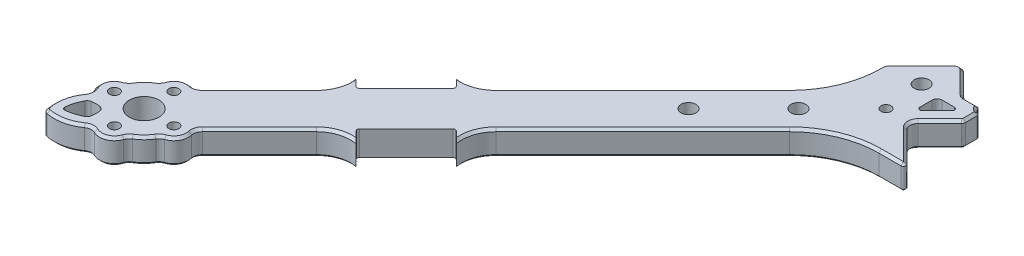
SolidWorks part; units mm, degrees
ref_plane "前视基准面" through (0, 0, 0) normal (0, 0, 1) x (1, 0, 0)
ref_plane "上视基准面" through (0, 0, 0) normal (0, 1, 0) x (1, 0, 0)
ref_plane "右视基准面" through (0, 0, 0) normal (1, 0, 0) x (0, 0, -1)
sketch "草图1" plane through (0, 0, 0) normal (0, 1, 0) x (1, 0, 0)
  line L0 (0, 0) -> (0, 44.7122) construction
  line L1 (-46.659, 0) -> (34.6836, 0) construction
  line L2 (3.067, 3.067) -> (44.142, 44.142) construction
  line L3 (0, 0) -> (-41.075, 41.075) construction
  line L4 (64.7943, 159.7121) -> (139.6536, 139.6536) construction
  line L5 (-139.6536, 139.6536) -> (-159.7121, 64.7943) construction
  line L6 (-159.7121, 64.7943) -> (-104.9113, 9.9936) construction
  line L7 (-104.9113, 9.9936) -> (-30.052, 30.052) construction
  line L8 (-30.052, 30.052) -> (-9.9936, 104.9113) construction
  line L9 (-9.9936, 104.9113) -> (-64.7943, 159.7121) construction
  line L10 (-64.7943, 159.7121) -> (-139.6536, 139.6536) construction
  line L11 (9.9936, 104.9113) -> (64.7943, 159.7121) construction
  line L12 (30.052, 30.052) -> (9.9936, 104.9113) construction
  line L13 (104.9113, 9.9936) -> (30.052, 30.052) construction
  line L14 (159.7121, 64.7943) -> (104.9113, 9.9936) construction
  line L15 (139.6536, 139.6536) -> (159.7121, 64.7943) construction
  line L16 (-64.7943, -159.7121) -> (-139.6536, -139.6536) construction
  line L17 (-9.9936, -104.9113) -> (-64.7943, -159.7121) construction
  line L18 (-30.052, -30.052) -> (-9.9936, -104.9113) construction
  line L19 (-104.9113, -9.9936) -> (-30.052, -30.052) construction
  line L20 (-159.7121, -64.7943) -> (-104.9113, -9.9936) construction
  line L21 (-139.6536, -139.6536) -> (-159.7121, -64.7943) construction
  line L22 (9.9936, -104.9113) -> (64.7943, -159.7121) construction
  line L23 (30.052, -30.052) -> (9.9936, -104.9113) construction
  line L24 (104.9113, -9.9936) -> (30.052, -30.052) construction
  line L25 (159.7121, -64.7943) -> (104.9113, -9.9936) construction
  line L26 (139.6536, -139.6536) -> (159.7121, -64.7943) construction
  line L27 (64.7943, -159.7121) -> (139.6536, -139.6536) construction
  line L28 (-90.8528, -84.8528) -> (-84.8528, -90.8528) construction
  line L29 (-10, 10) -> (10, 10) construction
  line L30 (-10, 10) -> (-10, -10) construction
  line L31 (-10, -10) -> (10, -10) construction
  line L32 (10, 10) -> (10, -10) construction
  line L33 (-10, 10) -> (10, -10) construction
  line L34 (-10, -10) -> (10, 10) construction
  line L35 (-90.8528, -84.8528) -> (-84.8528, -78.8528) construction
  line L36 (-84.8528, -90.8528) -> (-78.8528, -84.8528) construction
  line L37 (-84.8528, -78.8528) -> (-78.8528, -84.8528) construction
  line L38 (-90.8528, -84.8528) -> (-78.8528, -84.8528) construction
  line L39 (-84.8528, -90.8528) -> (-84.8528, -78.8528) construction
  line L40 (-83.3357, -76.2647) -> (-76.2647, -69.1936) construction
  line L41 (-76.2647, -83.3357) -> (-69.1936, -76.2647) construction
  line L42 (-40, -21.5) -> (-21.5, -40) construction
  line L43 (-25.5, 43.5) -> (25.5, 43.5) construction
  line L44 (-25.5, 43.5) -> (-25.5, -43.5) construction
  line L45 (-25.5, -43.5) -> (25.5, -43.5) construction
  line L46 (25.5, 43.5) -> (25.5, -43.5) construction
  line L47 (-25.5, 43.5) -> (25.5, -43.5) construction
  line L48 (-25.5, -43.5) -> (25.5, 43.5) construction
  line L49 (-21.5, -40) -> (-21.5, -21.5) construction
  line L50 (-1.05, -0.05) -> (-3.8789, -0.05)
  line L51 (-4.586, 0.2429) -> (-8.9393, 4.5962)
  line L52 (-0.05, -1.05) -> (-0.05, -3.8789) construction
  line L53 (-11.0607, 4.5962) -> (-17.4142, -1.7574)
  line L54 (-18, -3.1716) -> (-18, -3.4731)
  line L55 (-23.2721, -16.201) -> (-82.5161, -75.445)
  line L56 (-0.05, 1.05) -> (-0.05, 3.8789) construction
  line L57 (0.2429, 4.586) -> (4.5962, 8.9393) construction
  line L58 (4.5962, 11.0607) -> (-1.7574, 17.4142) construction
  line L59 (-3.1716, 18) -> (-3.4731, 18) construction
  line L60 (1.05, 0.05) -> (3.8789, 0.05) construction
  line L61 (4.586, -0.2429) -> (8.9393, -4.5962) construction
  line L62 (11.0607, -4.5962) -> (17.4142, 1.7574) construction
  line L63 (18, 3.1716) -> (18, 3.4731) construction
  line L64 (0.05, -1.05) -> (0.05, -3.8789) construction
  line L65 (-0.2429, -4.586) -> (-4.5962, -8.9393) construction
  line L66 (-4.5962, -11.0607) -> (1.7574, -17.4142) construction
  line L67 (3.1716, -18) -> (3.4731, -18) construction
  line L68 (-0.05, -1.05) -> (-0.05, -3.8789)
  line L69 (-0.3136, -4.5153) -> (-4.6669, -8.8686)
  line L70 (-75.445, -82.5161) -> (-16.201, -23.2721)
  line L71 (-3.4731, -18) -> (0.9946, -18)
  line L72 (3.1716, -18.1) -> (3.4731, -18.1) construction
  line L73 (-4.6669, -11.1314) -> (1.6866, -17.4849) construction
  line L74 (-4.6669, -11.1314) -> (1.3482, -17.1464)
  line L75 (-3.35, -2.85) -> (-5.85, -2.85)
  line L76 (-6.85, -3.85) -> (-6.85, -6.35)
  line L77 (-5.9964, -6.7036) -> (-2.9964, -3.7036)
  line L78 (-21.5, -40) -> (-38.3673, -19.8673) construction
  circle A0 centre (-84.8528, 84.8528) radius 77.5 construction
  circle A1 centre (-84.8528, 84.8528) radius 83 construction
  circle A2 centre (84.8528, 84.8528) radius 77.5 construction
  circle A3 centre (84.8528, 84.8528) radius 83 construction
  circle A4 centre (84.8528, -84.8528) radius 77.5 construction
  circle A5 centre (84.8528, -84.8528) radius 83 construction
  circle A6 centre (-84.8528, -84.8528) radius 83 construction
  circle A7 centre (-84.8528, -84.8528) radius 77.5 construction
  circle A8 centre (-84.8528, 84.8528) radius 67.117 construction
  circle A9 centre (10, 10) radius 1 construction
  circle A10 centre (-10, 10) radius 1 construction
  circle A11 centre (-10, -10) radius 1
  circle A12 centre (10, -10) radius 1 construction
  circle A13 centre (-84.8528, -84.8528) radius 6 construction
  circle A14 centre (-84.8528, -78.8528) radius 1
  circle A15 centre (-90.8528, -84.8528) radius 1
  circle A16 centre (-84.8528, -90.8528) radius 1
  circle A17 centre (-78.8528, -84.8528) radius 1
  circle A18 centre (-84.8528, -84.8528) radius 3
  circle A19 centre (-84.8528, -84.8528) radius 7 construction
  circle A20 centre (-84.8528, -78.8528) radius 3 construction
  circle A21 centre (-90.8528, -84.8528) radius 3 construction
  circle A22 centre (-84.8528, -90.8528) radius 3 construction
  circle A23 centre (-78.8528, -84.8528) radius 3 construction
  arc A24 (-84.1878, -75.9274) -> (-82.5161, -75.445) centre (-83.7889, -74.1722) ccw
  arc A25 (-84.1878, -75.9274) -> (-87.6956, -77.8945) centre (-84.8528, -78.8528) ccw
  arc A26 (-88.4709, -78.8604) -> (-90.8452, -81.2347) centre (-84.8528, -84.8528) ccw
  arc A27 (-91.8111, -82.01) -> (-93.5405, -86.1856) centre (-90.8528, -84.8528) ccw
  arc A28 (-90.8452, -81.2347) -> (-91.8111, -82.01) centre (-92.3861, -80.3043) cw
  arc A29 (-87.6956, -77.8945) -> (-88.4709, -78.8604) centre (-89.4013, -77.3195) cw
  arc A30 (-95.0261, -94.2399) -> (-93.6885, -88.0317) centre (-87.1792, -92.6823) cw
  arc A31 (-93.5405, -86.1856) -> (-93.6885, -88.0317) centre (-95.1531, -86.9853) cw
  arc A32 (-94.2399, -95.0261) -> (-88.0317, -93.6885) centre (-92.6823, -87.1792) ccw
  arc A33 (-86.1856, -93.5405) -> (-88.0317, -93.6885) centre (-86.9853, -95.1531) ccw
  arc A34 (-82.01, -91.8111) -> (-86.1856, -93.5405) centre (-84.8528, -90.8528) cw
  arc A35 (-81.2347, -90.8452) -> (-82.01, -91.8111) centre (-80.3043, -92.3861) ccw
  arc A36 (-78.8604, -88.4709) -> (-81.2347, -90.8452) centre (-84.8528, -84.8528) cw
  arc A37 (-77.8945, -87.6956) -> (-78.8604, -88.4709) centre (-77.3195, -89.4013) ccw
  arc A38 (-75.9274, -84.1878) -> (-77.8945, -87.6956) centre (-78.8528, -84.8528) cw
  arc A39 (-75.9274, -84.1878) -> (-75.445, -82.5161) centre (-74.1722, -83.7889) cw
  arc A40 (-95.0261, -94.2399) -> (-94.2399, -95.0261) centre (-94.0452, -94.0452) ccw
  arc A41 (-89.7377, -88.9059) -> (-91.477, -88.9335) centre (-90.5281, -93.9108) ccw
  arc A42 (-92.1608, -89.4245) -> (-93.1294, -92.591) centre (-85.4545, -93.2074) ccw
  arc A43 (-89.4245, -92.1608) -> (-92.591, -93.1294) centre (-93.2074, -85.4545) cw
  arc A44 (-88.9059, -89.7377) -> (-88.9335, -91.477) centre (-93.9108, -90.5281) cw
  arc A45 (-89.4245, -92.1608) -> (-88.9335, -91.477) centre (-89.9158, -91.2898) ccw
  arc A46 (-89.7377, -88.9059) -> (-88.9059, -89.7377) centre (-89.8937, -89.8937) cw
  arc A47 (-91.477, -88.9335) -> (-92.1608, -89.4245) centre (-91.2898, -89.9158) ccw
  arc A48 (-93.1294, -92.591) -> (-92.591, -93.1294) centre (-92.631, -92.631) ccw
  circle A49 centre (-21.5, -40) radius 3.1 construction
  circle A50 centre (-21.5, -40) radius 1.5 construction
  circle A51 centre (-40, -21.5) radius 1.5 construction
  circle A53 centre (-21.5, -21.5) radius 1.5 construction
  arc A54 (-3.8789, -0.05) -> (-4.586, 0.2429) centre (-3.8789, 0.95) cw
  arc A55 (-23.2721, -16.201) -> (-18, -3.4731) centre (-36, -3.4731) ccw
  arc A56 (-17.4142, -1.7574) -> (-18, -3.1716) centre (-16, -3.1716) ccw
  arc A57 (-8.9393, 4.5962) -> (-11.0607, 4.5962) centre (-10, 3.5355) ccw
  arc A58 (-1.05, -0.05) -> (-0.05, -1.05) centre (-1.05, -1.05) cw
  circle A59 centre (-10, 0) radius 1.5 construction
  arc A60 (-0.05, 3.8789) -> (0.2429, 4.586) centre (0.95, 3.8789) cw construction
  arc A61 (4.5962, 8.9393) -> (4.5962, 11.0607) centre (3.5355, 10) ccw construction
  arc A62 (-1.7574, 17.4142) -> (-3.1716, 18) centre (-3.1716, 16) ccw construction
  arc A63 (-16.201, 23.2721) -> (-3.4731, 18) centre (-3.4731, 36) ccw construction
  arc A64 (-0.05, 1.05) -> (-1.05, 0.05) centre (-1.05, 1.05) cw construction
  arc A65 (3.8789, 0.05) -> (4.586, -0.2429) centre (3.8789, -0.95) cw construction
  arc A66 (8.9393, -4.5962) -> (11.0607, -4.5962) centre (10, -3.5355) ccw construction
  arc A67 (17.4142, 1.7574) -> (18, 3.1716) centre (16, 3.1716) ccw construction
  arc A68 (23.2721, 16.201) -> (18, 3.4731) centre (36, 3.4731) ccw construction
  arc A69 (1.05, 0.05) -> (0.05, 1.05) centre (1.05, 1.05) cw construction
  arc A70 (0.05, -3.8789) -> (-0.2429, -4.586) centre (-0.95, -3.8789) cw construction
  arc A71 (-4.5962, -8.9393) -> (-4.5962, -11.0607) centre (-3.5355, -10) ccw construction
  arc A72 (1.7574, -17.4142) -> (3.1716, -18) centre (3.1716, -16) ccw construction
  arc A73 (16.201, -23.2721) -> (3.4731, -18) centre (3.4731, -36) ccw construction
  arc A74 (0.05, -1.05) -> (1.05, -0.05) centre (1.05, -1.05) cw construction
  arc A75 (-6.85, -6.35) -> (-5.9964, -6.7036) centre (-6.35, -6.35) ccw
  arc A76 (-0.05, -3.8789) -> (-0.3136, -4.5153) centre (-0.95, -3.8789) cw
  arc A77 (-4.6669, -8.8686) -> (-4.6669, -11.1314) centre (-3.5355, -10) ccw
  arc A78 (-16.201, -23.2721) -> (-3.4731, -18) centre (-3.4731, -36) cw
  arc A79 (0.9946, -18) -> (1.3482, -17.1464) centre (0.9946, -17.5) ccw
  arc A80 (16.1303, -23.3428) -> (3.4731, -18.1) centre (3.4731, -36) ccw construction
  arc A81 (1.6866, -17.4849) -> (3.1716, -18.1) centre (3.1716, -16) ccw construction
  arc A82 (-0.05, -1.05) -> (1.05, 0.05) centre (1.05, -1.05) cw construction
  arc A83 (-3.35, -2.85) -> (-2.9964, -3.7036) centre (-3.35, -3.35) cw
  arc A84 (-5.85, -2.85) -> (-6.85, -3.85) centre (-5.85, -3.85) ccw
  circle A87 centre (-38.3673, -19.8673) radius 1.5
  circle A88 centre (-38.3673, -19.8673) radius 2.4 construction
  circle A89 centre (-29.9337, -29.9337) radius 1.5
  circle A90 centre (-18.8388, -18.8388) radius 1.5
  circle A91 centre (-10.7071, -2.1213) radius 1.5
  circle A92 centre (-3.6338, -15.7) radius 1 construction
  point P47 (0, 0)
  point P85 (-91.1861, -81.8714)
  point P88 (-87.8342, -78.5195)
  point P95 (-94.8733, -94.8733)
  point P96 (-94.7523, -94.7523)
  point P115 (0, 0)
  point P122 (-89.0416, -91.9299)
  point P125 (-89.061, -89.061)
  point P128 (-91.9299, -89.0416)
  point P131 (-93.1539, -93.1539)
  point P158 (-10, 5.6569)
  point P163 (-0.05, -0.05)
  point P212 (0, 0)
  point P231 (-16.201, -23.2721)
  point P242 (-29.9337, -29.9337)
  dimension "D2" = 155
  dimension "D4" = 166
  dimension "D5" = 2
  dimension "D6" = 12
  dimension "D7" = 2
  dimension "D8" = 6
  dimension "D9" = 6
  dimension "D11" = 1.8
  dimension "D13" = 8
  dimension "D15" = 1
  dimension "D16" = 1
  dimension "D17" = 0.5
  dimension "D22" = 6.2
  dimension "D23" = 3
  dimension "D26" = 1
  dimension "D27" = 1
  dimension "D30" = 1.5
  dimension "D31" = 18
  dimension "D32" = 2
  dimension "D35" = 0.5
  dimension "D37" = 0.5
  dimension "D38" = 1
  dimension "D41" = 21.5
  dimension "D42" = 40
  dimension "D43" = 4.8
  dimension "D47" = 2
  dimension "D1" = 20
  dimension "D3" = 120
  dimension "D10" = 10
  dimension "D12" = 14
  dimension "D14" = 4
  dimension "D18" = 2
  dimension "D19" = 10
  dimension "D20" = 51
  dimension "D21" = 87
  dimension "D24" = 0.05
  dimension "D25" = 45
  dimension "D28" = 4
  dimension "D29" = 8
  dimension "D36" = 0.05
  dimension "D39" = 2.8
  dimension "D40" = 2.5
  dimension "D44" = 12.5
  dimension "D45" = 5
  dimension "D46" = 6
  dimension "D48" = 2.3
  dimension "D49" = 2.5
  dimension "D34" = 0.1
  dimension "D33" = 4
extrude "凸台-拉伸1" add sketch "草图1" along normal blind 5 contours L71 A79 L74 A77 L69 A76 L68 A58 L50 A54 L51 A57 L53 A56 L54 A55 L55 A24 A25 A29 A26 A28 A27 A31 A30 A40 A32 A33 A34 A35 A36 A37 A38 A39 L70 A78 A84 L75 A83 L77 A75 L76 A11 A14 A15 A16
sketch "草图2" plane through (0, 5, 0) normal (0, 1, 0) x (1, 0, 0)
  line L0 (-2.85, 3.35) -> (-2.85, 5.85)
  line L1 (-6.7036, 5.9964) -> (-3.7036, 2.9964)
  line L2 (-3.85, 6.85) -> (-6.35, 6.85)
  line L3 (-3.35, -2.85) -> (-5.85, -2.85)
  line L4 (-5.9964, -6.7036) -> (-2.9964, -3.7036)
  line L5 (-6.85, -3.85) -> (-6.85, -6.35)
  line L6 (-3.35, -2.85) -> (-5.85, -2.85)
  line L7 (-5.9964, -6.7036) -> (-2.9964, -3.7036)
  line L8 (-6.85, -3.85) -> (-6.85, -6.35)
  line L9 (-18, 3.4731) -> (-18, -0.9946)
  line L10 (-17.1464, -1.3482) -> (-11.1314, 4.6669)
  line L11 (-8.8686, 4.6669) -> (-4.5153, 0.3136)
  line L12 (-3.8789, 0.05) -> (-1.05, 0.05)
  line L13 (-0.05, 1.05) -> (-0.05, 3.8789)
  line L14 (0.2429, 4.586) -> (4.5962, 8.9393)
  line L15 (4.5962, 11.0607) -> (-1.7574, 17.4142)
  line L16 (-3.4731, -18) -> (0.9946, -18)
  line L17 (1.3482, -17.1464) -> (-4.6669, -11.1314)
  line L18 (-4.6669, -8.8686) -> (-0.3136, -4.5153)
  line L19 (-0.05, -3.8789) -> (-0.05, -1.05)
  line L20 (-1.05, -0.05) -> (-3.8789, -0.05)
  line L21 (-4.586, 0.2429) -> (-8.9393, 4.5962)
  line L22 (-11.0607, 4.5962) -> (-17.4142, -1.7574)
  line L23 (-18, -3.1716) -> (-18, -3.4731)
  line L24 (-23.2721, -16.201) -> (-82.5161, -75.445)
  line L25 (-75.445, -82.5161) -> (-16.201, -23.2721)
  line L26 (-3.4731, -18) -> (0.9946, -18)
  line L27 (1.3482, -17.1464) -> (-4.6669, -11.1314)
  line L28 (-4.6669, -8.8686) -> (-0.3136, -4.5153)
  line L29 (-0.05, -3.8789) -> (-0.05, -1.05)
  line L30 (-1.05, -0.05) -> (-3.8789, -0.05)
  line L31 (-4.586, 0.2429) -> (-8.9393, 4.5962)
  line L32 (-11.0607, 4.5962) -> (-17.4142, -1.7574)
  line L33 (-18, -3.1716) -> (-18, -3.4731)
  line L34 (-23.2721, -16.201) -> (-82.5161, -75.445)
  line L35 (-75.445, -82.5161) -> (-16.201, -23.2721)
  line L36 (-3.1716, 18) -> (-3.4731, 18)
  line L37 (-16.201, 23.2721) -> (-75.445, 82.5161)
  line L38 (-82.5161, 75.445) -> (-23.2721, 16.201)
  line L39 (3.35, 2.85) -> (5.85, 2.85)
  line L40 (5.9964, 6.7036) -> (2.9964, 3.7036)
  line L41 (6.85, 3.85) -> (6.85, 6.35)
  line L42 (3.4731, 18) -> (-0.9946, 18)
  line L43 (-1.3482, 17.1464) -> (4.6669, 11.1314)
  line L44 (4.6669, 8.8686) -> (0.3136, 4.5153)
  line L45 (0.05, 3.8789) -> (0.05, 1.05)
  line L46 (1.05, 0.05) -> (3.8789, 0.05)
  line L47 (4.586, -0.2429) -> (8.9393, -4.5962)
  line L48 (11.0607, -4.5962) -> (17.4142, 1.7574)
  line L49 (18, 3.1716) -> (18, 3.4731)
  line L50 (23.2721, 16.201) -> (82.5161, 75.445)
  line L51 (75.445, 82.5161) -> (16.201, 23.2721)
  line L52 (2.85, -3.35) -> (2.85, -5.85)
  line L53 (6.7036, -5.9964) -> (3.7036, -2.9964)
  line L54 (3.85, -6.85) -> (6.35, -6.85)
  line L55 (18, -3.4731) -> (18, 0.9946)
  line L56 (17.1464, 1.3482) -> (11.1314, -4.6669)
  line L57 (8.8686, -4.6669) -> (4.5153, -0.3136)
  line L58 (3.8789, -0.05) -> (1.05, -0.05)
  line L59 (0.05, -1.05) -> (0.05, -3.8789)
  line L60 (-0.2429, -4.586) -> (-4.5962, -8.9393)
  line L61 (-4.5962, -11.0607) -> (1.7574, -17.4142)
  line L62 (3.1716, -18) -> (3.4731, -18)
  line L63 (16.201, -23.2721) -> (75.445, -82.5161)
  line L64 (82.5161, -75.445) -> (23.2721, -16.201)
  line L65 (-25.5, 43.5) -> (25.5, -43.5) construction
  line L66 (25.5, 43.5) -> (-25.5, 43.5) construction
  line L67 (25.5, 43.5) -> (25.5, -43.5) construction
  line L68 (25.5, -43.5) -> (-25.5, -43.5) construction
  line L69 (-25.5, 43.5) -> (-25.5, -43.5) construction
  line L70 (25.5, 43.5) -> (-25.5, -43.5) construction
  line L71 (25.5, -43.5) -> (-25.5, 43.5) construction
  circle A0 centre (-10, 10) radius 1
  circle A1 centre (-10, -10) radius 1
  circle A2 centre (-10, -10) radius 1
  arc A3 (-5.85, -2.85) -> (-6.85, -3.85) centre (-5.85, -3.85) ccw
  arc A4 (-2.9964, -3.7036) -> (-3.35, -2.85) centre (-3.35, -3.35) ccw
  arc A5 (-6.85, -6.35) -> (-5.9964, -6.7036) centre (-6.35, -6.35) ccw
  arc A6 (-5.85, -2.85) -> (-6.85, -3.85) centre (-5.85, -3.85) ccw
  arc A7 (-2.9964, -3.7036) -> (-3.35, -2.85) centre (-3.35, -3.35) ccw
  arc A8 (-6.85, -6.35) -> (-5.9964, -6.7036) centre (-6.35, -6.35) ccw
  circle A9 centre (-84.8528, -78.8528) radius 1
  circle A10 centre (-84.8528, -78.8528) radius 1
  circle A11 centre (-90.8528, -84.8528) radius 1
  circle A12 centre (-90.8528, -84.8528) radius 1
  circle A13 centre (-84.8528, -90.8528) radius 1
  circle A14 centre (-84.8528, -90.8528) radius 1
  circle A15 centre (-78.8528, -84.8528) radius 1
  circle A16 centre (-78.8528, -84.8528) radius 1
  circle A17 centre (-84.8528, -84.8528) radius 3
  circle A18 centre (-84.8528, -84.8528) radius 3
  circle A19 centre (-29.9337, -29.9337) radius 1.5 construction
  circle A21 centre (-18.8388, -18.8388) radius 1.5 construction
  arc A25 (-2.85, 5.85) -> (-3.85, 6.85) centre (-3.85, 5.85) ccw
  arc A26 (-93.1294, -92.591) -> (-92.591, -93.1294) centre (-92.631, -92.631) ccw
  arc A27 (-92.1608, -89.4245) -> (-93.1294, -92.591) centre (-85.4545, -93.2074) ccw
  arc A28 (-91.477, -88.9335) -> (-92.1608, -89.4245) centre (-91.2898, -89.9158) ccw
  arc A29 (-89.7377, -88.9059) -> (-91.477, -88.9335) centre (-90.5281, -93.9108) ccw
  arc A30 (-88.9059, -89.7377) -> (-89.7377, -88.9059) centre (-89.8937, -89.8937) ccw
  arc A31 (-88.9335, -91.477) -> (-88.9059, -89.7377) centre (-93.9108, -90.5281) ccw
  arc A32 (-89.4245, -92.1608) -> (-88.9335, -91.477) centre (-89.9158, -91.2898) ccw
  arc A33 (-92.591, -93.1294) -> (-89.4245, -92.1608) centre (-93.2074, -85.4545) ccw
  arc A34 (-93.1294, -92.591) -> (-92.591, -93.1294) centre (-92.631, -92.631) ccw
  arc A35 (-92.1608, -89.4245) -> (-93.1294, -92.591) centre (-85.4545, -93.2074) ccw
  arc A36 (-91.477, -88.9335) -> (-92.1608, -89.4245) centre (-91.2898, -89.9158) ccw
  arc A37 (-89.7377, -88.9059) -> (-91.477, -88.9335) centre (-90.5281, -93.9108) ccw
  arc A38 (-88.9059, -89.7377) -> (-89.7377, -88.9059) centre (-89.8937, -89.8937) ccw
  arc A39 (-88.9335, -91.477) -> (-88.9059, -89.7377) centre (-93.9108, -90.5281) ccw
  arc A40 (-89.4245, -92.1608) -> (-88.9335, -91.477) centre (-89.9158, -91.2898) ccw
  arc A41 (-92.591, -93.1294) -> (-89.4245, -92.1608) centre (-93.2074, -85.4545) ccw
  arc A42 (-3.7036, 2.9964) -> (-2.85, 3.35) centre (-3.35, 3.35) ccw
  arc A43 (-6.35, 6.85) -> (-6.7036, 5.9964) centre (-6.35, 6.35) ccw
  circle A44 centre (-78.8528, 84.8528) radius 1
  circle A45 centre (-84.8528, 90.8528) radius 1
  circle A46 centre (-90.8528, 84.8528) radius 1
  circle A47 centre (-84.8528, 78.8528) radius 1
  circle A48 centre (-84.8528, 84.8528) radius 3
  arc A52 (-92.591, 93.1294) -> (-93.1294, 92.591) centre (-92.631, 92.631) ccw
  arc A53 (-89.4245, 92.1608) -> (-92.591, 93.1294) centre (-93.2074, 85.4545) ccw
  arc A54 (-88.9335, 91.477) -> (-89.4245, 92.1608) centre (-89.9158, 91.2898) ccw
  arc A55 (-88.9059, 89.7377) -> (-88.9335, 91.477) centre (-93.9108, 90.5281) ccw
  arc A56 (-89.7377, 88.9059) -> (-88.9059, 89.7377) centre (-89.8937, 89.8937) ccw
  arc A57 (-91.477, 88.9335) -> (-89.7377, 88.9059) centre (-90.5281, 93.9108) ccw
  arc A58 (-92.1608, 89.4245) -> (-91.477, 88.9335) centre (-91.2898, 89.9158) ccw
  arc A59 (-93.1294, 92.591) -> (-92.1608, 89.4245) centre (-85.4545, 93.2074) ccw
  arc A60 (-18, -0.9946) -> (-17.1464, -1.3482) centre (-17.5, -0.9946) ccw
  arc A61 (-8.8686, 4.6669) -> (-11.1314, 4.6669) centre (-10, 3.5355) ccw
  arc A62 (-4.5153, 0.3136) -> (-3.8789, 0.05) centre (-3.8789, 0.95) ccw
  arc A63 (-1.05, 0.05) -> (-0.05, 1.05) centre (-1.05, 1.05) ccw
  arc A64 (0.2429, 4.586) -> (-0.05, 3.8789) centre (0.95, 3.8789) ccw
  arc A65 (4.5962, 8.9393) -> (4.5962, 11.0607) centre (3.5355, 10) ccw
  arc A66 (0.9946, -18) -> (1.3482, -17.1464) centre (0.9946, -17.5) ccw
  arc A67 (-4.6669, -8.8686) -> (-4.6669, -11.1314) centre (-3.5355, -10) ccw
  arc A68 (-0.3136, -4.5153) -> (-0.05, -3.8789) centre (-0.95, -3.8789) ccw
  arc A69 (-0.05, -1.05) -> (-1.05, -0.05) centre (-1.05, -1.05) ccw
  arc A70 (-4.586, 0.2429) -> (-3.8789, -0.05) centre (-3.8789, 0.95) ccw
  arc A71 (-8.9393, 4.5962) -> (-11.0607, 4.5962) centre (-10, 3.5355) ccw
  arc A72 (-17.4142, -1.7574) -> (-18, -3.1716) centre (-16, -3.1716) ccw
  arc A73 (-23.2721, -16.201) -> (-18, -3.4731) centre (-36, -3.4731) ccw
  arc A74 (-84.1878, -75.9274) -> (-82.5161, -75.445) centre (-83.7889, -74.1722) ccw
  arc A75 (-84.1878, -75.9274) -> (-87.6956, -77.8945) centre (-84.8528, -78.8528) ccw
  arc A76 (-88.4709, -78.8604) -> (-87.6956, -77.8945) centre (-89.4013, -77.3195) ccw
  arc A77 (-88.4709, -78.8604) -> (-90.8452, -81.2347) centre (-84.8528, -84.8528) ccw
  arc A78 (-91.8111, -82.01) -> (-90.8452, -81.2347) centre (-92.3861, -80.3043) ccw
  arc A79 (-91.8111, -82.01) -> (-93.5405, -86.1856) centre (-90.8528, -84.8528) ccw
  arc A80 (-93.6885, -88.0317) -> (-93.5405, -86.1856) centre (-95.1531, -86.9853) ccw
  arc A81 (-93.6885, -88.0317) -> (-95.0261, -94.2399) centre (-87.1792, -92.6823) ccw
  arc A82 (-95.0261, -94.2399) -> (-94.2399, -95.0261) centre (-94.0452, -94.0452) ccw
  arc A83 (-94.2399, -95.0261) -> (-88.0317, -93.6885) centre (-92.6823, -87.1792) ccw
  arc A84 (-86.1856, -93.5405) -> (-88.0317, -93.6885) centre (-86.9853, -95.1531) ccw
  arc A85 (-86.1856, -93.5405) -> (-82.01, -91.8111) centre (-84.8528, -90.8528) ccw
  arc A86 (-81.2347, -90.8452) -> (-82.01, -91.8111) centre (-80.3043, -92.3861) ccw
  arc A87 (-81.2347, -90.8452) -> (-78.8604, -88.4709) centre (-84.8528, -84.8528) ccw
  arc A88 (-77.8945, -87.6956) -> (-78.8604, -88.4709) centre (-77.3195, -89.4013) ccw
  arc A89 (-77.8945, -87.6956) -> (-75.9274, -84.1878) centre (-78.8528, -84.8528) ccw
  arc A90 (-75.445, -82.5161) -> (-75.9274, -84.1878) centre (-74.1722, -83.7889) ccw
  arc A91 (-3.4731, -18) -> (-16.201, -23.2721) centre (-3.4731, -36) ccw
  arc A92 (0.9946, -18) -> (1.3482, -17.1464) centre (0.9946, -17.5) ccw
  arc A93 (-4.6669, -8.8686) -> (-4.6669, -11.1314) centre (-3.5355, -10) ccw
  arc A94 (-0.3136, -4.5153) -> (-0.05, -3.8789) centre (-0.95, -3.8789) ccw
  arc A95 (-0.05, -1.05) -> (-1.05, -0.05) centre (-1.05, -1.05) ccw
  arc A96 (-4.586, 0.2429) -> (-3.8789, -0.05) centre (-3.8789, 0.95) ccw
  arc A97 (-8.9393, 4.5962) -> (-11.0607, 4.5962) centre (-10, 3.5355) ccw
  arc A98 (-17.4142, -1.7574) -> (-18, -3.1716) centre (-16, -3.1716) ccw
  arc A99 (-23.2721, -16.201) -> (-18, -3.4731) centre (-36, -3.4731) ccw
  arc A100 (-84.1878, -75.9274) -> (-82.5161, -75.445) centre (-83.7889, -74.1722) ccw
  arc A101 (-84.1878, -75.9274) -> (-87.6956, -77.8945) centre (-84.8528, -78.8528) ccw
  arc A102 (-88.4709, -78.8604) -> (-87.6956, -77.8945) centre (-89.4013, -77.3195) ccw
  arc A103 (-88.4709, -78.8604) -> (-90.8452, -81.2347) centre (-84.8528, -84.8528) ccw
  arc A104 (-91.8111, -82.01) -> (-90.8452, -81.2347) centre (-92.3861, -80.3043) ccw
  arc A105 (-91.8111, -82.01) -> (-93.5405, -86.1856) centre (-90.8528, -84.8528) ccw
  arc A106 (-93.6885, -88.0317) -> (-93.5405, -86.1856) centre (-95.1531, -86.9853) ccw
  arc A107 (-93.6885, -88.0317) -> (-95.0261, -94.2399) centre (-87.1792, -92.6823) ccw
  arc A108 (-95.0261, -94.2399) -> (-94.2399, -95.0261) centre (-94.0452, -94.0452) ccw
  arc A109 (-94.2399, -95.0261) -> (-88.0317, -93.6885) centre (-92.6823, -87.1792) ccw
  arc A110 (-86.1856, -93.5405) -> (-88.0317, -93.6885) centre (-86.9853, -95.1531) ccw
  arc A111 (-86.1856, -93.5405) -> (-82.01, -91.8111) centre (-84.8528, -90.8528) ccw
  arc A112 (-81.2347, -90.8452) -> (-82.01, -91.8111) centre (-80.3043, -92.3861) ccw
  arc A113 (-81.2347, -90.8452) -> (-78.8604, -88.4709) centre (-84.8528, -84.8528) ccw
  arc A114 (-77.8945, -87.6956) -> (-78.8604, -88.4709) centre (-77.3195, -89.4013) ccw
  arc A115 (-77.8945, -87.6956) -> (-75.9274, -84.1878) centre (-78.8528, -84.8528) ccw
  arc A116 (-75.445, -82.5161) -> (-75.9274, -84.1878) centre (-74.1722, -83.7889) ccw
  arc A117 (-3.4731, -18) -> (-16.201, -23.2721) centre (-3.4731, -36) ccw
  arc A118 (-1.7574, 17.4142) -> (-3.1716, 18) centre (-3.1716, 16) ccw
  arc A119 (-16.201, 23.2721) -> (-3.4731, 18) centre (-3.4731, 36) ccw
  arc A120 (-75.9274, 84.1878) -> (-75.445, 82.5161) centre (-74.1722, 83.7889) ccw
  arc A121 (-75.9274, 84.1878) -> (-77.8945, 87.6956) centre (-78.8528, 84.8528) ccw
  arc A122 (-78.8604, 88.4709) -> (-77.8945, 87.6956) centre (-77.3195, 89.4013) ccw
  arc A123 (-78.8604, 88.4709) -> (-81.2347, 90.8452) centre (-84.8528, 84.8528) ccw
  arc A124 (-82.01, 91.8111) -> (-81.2347, 90.8452) centre (-80.3043, 92.3861) ccw
  arc A125 (-82.01, 91.8111) -> (-86.1856, 93.5405) centre (-84.8528, 90.8528) ccw
  arc A126 (-88.0317, 93.6885) -> (-86.1856, 93.5405) centre (-86.9853, 95.1531) ccw
  arc A127 (-88.0317, 93.6885) -> (-94.2399, 95.0261) centre (-92.6823, 87.1792) ccw
  arc A128 (-94.2399, 95.0261) -> (-95.0261, 94.2399) centre (-94.0452, 94.0452) ccw
  arc A129 (-95.0261, 94.2399) -> (-93.6885, 88.0317) centre (-87.1792, 92.6823) ccw
  arc A130 (-93.5405, 86.1856) -> (-93.6885, 88.0317) centre (-95.1531, 86.9853) ccw
  arc A131 (-93.5405, 86.1856) -> (-91.8111, 82.01) centre (-90.8528, 84.8528) ccw
  arc A132 (-90.8452, 81.2347) -> (-91.8111, 82.01) centre (-92.3861, 80.3043) ccw
  arc A133 (-90.8452, 81.2347) -> (-88.4709, 78.8604) centre (-84.8528, 84.8528) ccw
  arc A134 (-87.6956, 77.8945) -> (-88.4709, 78.8604) centre (-89.4013, 77.3195) ccw
  arc A135 (-87.6956, 77.8945) -> (-84.1878, 75.9274) centre (-84.8528, 78.8528) ccw
  arc A136 (-82.5161, 75.445) -> (-84.1878, 75.9274) centre (-83.7889, 74.1722) ccw
  arc A137 (-18, 3.4731) -> (-23.2721, 16.201) centre (-36, 3.4731) ccw
  circle A138 centre (10, 10) radius 1
  arc A139 (5.85, 2.85) -> (6.85, 3.85) centre (5.85, 3.85) ccw
  arc A140 (2.9964, 3.7036) -> (3.35, 2.85) centre (3.35, 3.35) ccw
  arc A141 (6.85, 6.35) -> (5.9964, 6.7036) centre (6.35, 6.35) ccw
  circle A142 centre (84.8528, 78.8528) radius 1
  circle A143 centre (90.8528, 84.8528) radius 1
  circle A144 centre (84.8528, 90.8528) radius 1
  circle A145 centre (78.8528, 84.8528) radius 1
  circle A146 centre (84.8528, 84.8528) radius 3
  arc A150 (93.1294, 92.591) -> (92.591, 93.1294) centre (92.631, 92.631) ccw
  arc A151 (92.1608, 89.4245) -> (93.1294, 92.591) centre (85.4545, 93.2074) ccw
  arc A152 (91.477, 88.9335) -> (92.1608, 89.4245) centre (91.2898, 89.9158) ccw
  arc A153 (89.7377, 88.9059) -> (91.477, 88.9335) centre (90.5281, 93.9108) ccw
  arc A154 (88.9059, 89.7377) -> (89.7377, 88.9059) centre (89.8937, 89.8937) ccw
  arc A155 (88.9335, 91.477) -> (88.9059, 89.7377) centre (93.9108, 90.5281) ccw
  arc A156 (89.4245, 92.1608) -> (88.9335, 91.477) centre (89.9158, 91.2898) ccw
  arc A157 (92.591, 93.1294) -> (89.4245, 92.1608) centre (93.2074, 85.4545) ccw
  arc A158 (-0.9946, 18) -> (-1.3482, 17.1464) centre (-0.9946, 17.5) ccw
  arc A159 (4.6669, 8.8686) -> (4.6669, 11.1314) centre (3.5355, 10) ccw
  arc A160 (0.3136, 4.5153) -> (0.05, 3.8789) centre (0.95, 3.8789) ccw
  arc A161 (0.05, 1.05) -> (1.05, 0.05) centre (1.05, 1.05) ccw
  arc A162 (4.586, -0.2429) -> (3.8789, 0.05) centre (3.8789, -0.95) ccw
  arc A163 (8.9393, -4.5962) -> (11.0607, -4.5962) centre (10, -3.5355) ccw
  arc A164 (17.4142, 1.7574) -> (18, 3.1716) centre (16, 3.1716) ccw
  arc A165 (23.2721, 16.201) -> (18, 3.4731) centre (36, 3.4731) ccw
  arc A166 (84.1878, 75.9274) -> (82.5161, 75.445) centre (83.7889, 74.1722) ccw
  arc A167 (84.1878, 75.9274) -> (87.6956, 77.8945) centre (84.8528, 78.8528) ccw
  arc A168 (88.4709, 78.8604) -> (87.6956, 77.8945) centre (89.4013, 77.3195) ccw
  arc A169 (88.4709, 78.8604) -> (90.8452, 81.2347) centre (84.8528, 84.8528) ccw
  arc A170 (91.8111, 82.01) -> (90.8452, 81.2347) centre (92.3861, 80.3043) ccw
  arc A171 (91.8111, 82.01) -> (93.5405, 86.1856) centre (90.8528, 84.8528) ccw
  arc A172 (93.6885, 88.0317) -> (93.5405, 86.1856) centre (95.1531, 86.9853) ccw
  arc A173 (93.6885, 88.0317) -> (95.0261, 94.2399) centre (87.1792, 92.6823) ccw
  arc A174 (95.0261, 94.2399) -> (94.2399, 95.0261) centre (94.0452, 94.0452) ccw
  arc A175 (94.2399, 95.0261) -> (88.0317, 93.6885) centre (92.6823, 87.1792) ccw
  arc A176 (86.1856, 93.5405) -> (88.0317, 93.6885) centre (86.9853, 95.1531) ccw
  arc A177 (86.1856, 93.5405) -> (82.01, 91.8111) centre (84.8528, 90.8528) ccw
  arc A178 (81.2347, 90.8452) -> (82.01, 91.8111) centre (80.3043, 92.3861) ccw
  arc A179 (81.2347, 90.8452) -> (78.8604, 88.4709) centre (84.8528, 84.8528) ccw
  arc A180 (77.8945, 87.6956) -> (78.8604, 88.4709) centre (77.3195, 89.4013) ccw
  arc A181 (77.8945, 87.6956) -> (75.9274, 84.1878) centre (78.8528, 84.8528) ccw
  arc A182 (75.445, 82.5161) -> (75.9274, 84.1878) centre (74.1722, 83.7889) ccw
  arc A183 (3.4731, 18) -> (16.201, 23.2721) centre (3.4731, 36) ccw
  circle A184 centre (10, -10) radius 1
  arc A185 (2.85, -5.85) -> (3.85, -6.85) centre (3.85, -5.85) ccw
  arc A186 (3.7036, -2.9964) -> (2.85, -3.35) centre (3.35, -3.35) ccw
  arc A187 (6.35, -6.85) -> (6.7036, -5.9964) centre (6.35, -6.35) ccw
  circle A188 centre (78.8528, -84.8528) radius 1
  circle A189 centre (84.8528, -90.8528) radius 1
  circle A190 centre (90.8528, -84.8528) radius 1
  circle A191 centre (84.8528, -78.8528) radius 1
  circle A192 centre (84.8528, -84.8528) radius 3
  arc A196 (92.591, -93.1294) -> (93.1294, -92.591) centre (92.631, -92.631) ccw
  arc A197 (89.4245, -92.1608) -> (92.591, -93.1294) centre (93.2074, -85.4545) ccw
  arc A198 (88.9335, -91.477) -> (89.4245, -92.1608) centre (89.9158, -91.2898) ccw
  arc A199 (88.9059, -89.7377) -> (88.9335, -91.477) centre (93.9108, -90.5281) ccw
  arc A200 (89.7377, -88.9059) -> (88.9059, -89.7377) centre (89.8937, -89.8937) ccw
  arc A201 (91.477, -88.9335) -> (89.7377, -88.9059) centre (90.5281, -93.9108) ccw
  arc A202 (92.1608, -89.4245) -> (91.477, -88.9335) centre (91.2898, -89.9158) ccw
  arc A203 (93.1294, -92.591) -> (92.1608, -89.4245) centre (85.4545, -93.2074) ccw
  arc A204 (18, 0.9946) -> (17.1464, 1.3482) centre (17.5, 0.9946) ccw
  arc A205 (8.8686, -4.6669) -> (11.1314, -4.6669) centre (10, -3.5355) ccw
  arc A206 (4.5153, -0.3136) -> (3.8789, -0.05) centre (3.8789, -0.95) ccw
  arc A207 (1.05, -0.05) -> (0.05, -1.05) centre (1.05, -1.05) ccw
  arc A208 (-0.2429, -4.586) -> (0.05, -3.8789) centre (-0.95, -3.8789) ccw
  arc A209 (-4.5962, -8.9393) -> (-4.5962, -11.0607) centre (-3.5355, -10) ccw
  arc A210 (1.7574, -17.4142) -> (3.1716, -18) centre (3.1716, -16) ccw
  arc A211 (16.201, -23.2721) -> (3.4731, -18) centre (3.4731, -36) ccw
  arc A212 (75.9274, -84.1878) -> (75.445, -82.5161) centre (74.1722, -83.7889) ccw
  arc A213 (75.9274, -84.1878) -> (77.8945, -87.6956) centre (78.8528, -84.8528) ccw
  arc A214 (78.8604, -88.4709) -> (77.8945, -87.6956) centre (77.3195, -89.4013) ccw
  arc A215 (78.8604, -88.4709) -> (81.2347, -90.8452) centre (84.8528, -84.8528) ccw
  arc A216 (82.01, -91.8111) -> (81.2347, -90.8452) centre (80.3043, -92.3861) ccw
  arc A217 (82.01, -91.8111) -> (86.1856, -93.5405) centre (84.8528, -90.8528) ccw
  arc A218 (88.0317, -93.6885) -> (86.1856, -93.5405) centre (86.9853, -95.1531) ccw
  arc A219 (88.0317, -93.6885) -> (94.2399, -95.0261) centre (92.6823, -87.1792) ccw
  arc A220 (94.2399, -95.0261) -> (95.0261, -94.2399) centre (94.0452, -94.0452) ccw
  arc A221 (95.0261, -94.2399) -> (93.6885, -88.0317) centre (87.1792, -92.6823) ccw
  arc A222 (93.5405, -86.1856) -> (93.6885, -88.0317) centre (95.1531, -86.9853) ccw
  arc A223 (93.5405, -86.1856) -> (91.8111, -82.01) centre (90.8528, -84.8528) ccw
  arc A224 (90.8452, -81.2347) -> (91.8111, -82.01) centre (92.3861, -80.3043) ccw
  arc A225 (90.8452, -81.2347) -> (88.4709, -78.8604) centre (84.8528, -84.8528) ccw
  arc A226 (87.6956, -77.8945) -> (88.4709, -78.8604) centre (89.4013, -77.3195) ccw
  arc A227 (87.6956, -77.8945) -> (84.1878, -75.9274) centre (84.8528, -78.8528) ccw
  arc A228 (82.5161, -75.445) -> (84.1878, -75.9274) centre (83.7889, -74.1722) ccw
  arc A229 (18, -3.4731) -> (23.2721, -16.201) centre (36, -3.4731) ccw
  circle A234 centre (-10.7071, -2.1213) radius 1.5 construction
  circle A235 centre (-29.9337, -29.9337) radius 1.5
  circle A236 centre (-18.8388, -18.8388) radius 1.5
  circle A238 centre (-10.7071, -2.1213) radius 1.5
  circle A239 centre (-38.3673, -19.8673) radius 1.5 construction
  circle A240 centre (-38.3673, -19.8673) radius 1.5
  circle A241 centre (-21.5, -40) radius 1.5 construction
  circle A242 centre (-21.5, -40) radius 1.5
  circle A243 centre (29.9337, -29.9337) radius 1.5 construction
  circle A244 centre (-29.9337, 29.9337) radius 1.5 construction
  circle A245 centre (29.9337, 29.9337) radius 1.5 construction
  circle A246 centre (18.8388, 18.8388) radius 1.5 construction
  circle A247 centre (18.8388, -18.8388) radius 1.5 construction
  circle A248 centre (-18.8388, 18.8388) radius 1.5 construction
  circle A252 centre (2.1213, -10.7071) radius 1.5 construction
  circle A253 centre (-2.1213, 10.7071) radius 1.5 construction
  circle A254 centre (10.7071, 2.1213) radius 1.5 construction
  circle A255 centre (29.9337, -29.9337) radius 1.5
  circle A256 centre (-29.9337, 29.9337) radius 1.5
  circle A257 centre (29.9337, 29.9337) radius 1.5
  circle A258 centre (18.8388, 18.8388) radius 1.5
  circle A259 centre (18.8388, -18.8388) radius 1.5
  circle A260 centre (-18.8388, 18.8388) radius 1.5
  circle A264 centre (2.1213, -10.7071) radius 1.5
  circle A265 centre (-2.1213, 10.7071) radius 1.5
  circle A266 centre (10.7071, 2.1213) radius 1.5
  point P432 (0, 0)
  point P436 (0, 0)
  dimension "D15" = 0.1
  dimension "D14" = 0.1
  dimension "D1" = 0
  dimension "D2" = 0
  dimension "D3" = 0
  dimension "D4" = 0
  dimension "D5" = 0
  dimension "D6" = 0
  dimension "D7" = 0
  dimension "D8" = 0
  dimension "D12" = 0
  dimension "D13" = 4
sketch "草图3" plane through (0, 0, 0) normal (0, -1, 0) x (1, 0, 0)
  line L0 (25.5, 43.5) -> (-25.5, -43.5) construction
  circle A0 centre (0, 0) radius 1.2
  dimension "D1" = 2.4
extrude "切除-拉伸1" cut sketch "草图3" against normal through all
fillet "圆角1" radius 0.5 2 edges at (-1.199, 2.5, 0.05) (-0.05, 2.5, 1.199)
sketch "草图4" plane through (0, 5, 0) normal (0, 1, 0) x (1, 0, 0)
  line L0 (-59.0191, -47.7053) -> (-56.8977, -49.8267)
  line L1 (-47.7053, -59.0191) -> (-59.0191, -47.7053) construction
  line L2 (-56.8977, -49.8267) -> (-52.8941, -45.823)
  line L3 (-23.2721, -16.201) -> (-82.5161, -75.445) construction
  line L4 (-65.1326, -51.6976) -> (-51.6976, -65.1326) construction
  line L5 (-61.1404, -47.7053) -> (-69.1248, -55.6898) construction
  line L6 (-55.6898, -69.1248) -> (-47.7053, -61.1404) construction
  line L7 (-53.3622, -53.3622) -> (-63.468, -63.468) construction
  line L8 (-69.1248, -57.8111) -> (-57.8111, -69.1248) construction
  line L9 (-67.0035, -59.9325) -> (-71.0072, -63.9361)
  line L10 (-69.1248, -57.8111) -> (-67.0035, -59.9325)
  line L11 (-57.8111, -69.1248) -> (-59.9325, -67.0035)
  line L12 (-59.9325, -67.0035) -> (-63.9361, -71.0072)
  line L13 (-49.8267, -56.8977) -> (-45.823, -52.8941)
  line L14 (-47.7053, -59.0191) -> (-49.8267, -56.8977)
  arc A0 (-52.8941, -45.823) -> (-59.0191, -47.7053) centre (-57.7329, -40.9842) cw
  arc A1 (-71.0072, -63.9361) -> (-69.1248, -57.8111) centre (-75.846, -59.0973) ccw
  arc A2 (-63.9361, -71.0072) -> (-57.8111, -69.1248) centre (-59.0973, -75.846) cw
  arc A3 (-45.823, -52.8941) -> (-47.7053, -59.0191) centre (-40.9842, -57.7329) ccw
  point P19 (-53.3622, -53.3622)
  point P32 (0, 0)
  point P33 (0, 0)
extrude "凸台-拉伸2" add sketch "草图4" against normal up to surface (5 mm away) up to face at (-10.7071, 0, 3.6213)
chamfer "倒角1" distance 0.5 angle 45 88 edges at (-6.7627, 0, -2.4195) (-6.7627, 5, -2.4195) (-4.2616, 0, -0.0261) (-4.2616, 5, -0.0261) (-10, 0, -5.0355) (-10, 5, -5.0355) (-2.7438, 5, 0.05) (-2.7438, 0, 0.05) (-14.2374, 0, -1.4194) (-14.2374, 5, -1.4194) (-17.8478, 0, 2.4062) (-17.8478, 5, 2.4062) (-0.05, 0, 2.7438) (-0.05, 5, 2.7438) (-18, 0, 3.3223) (-18, 5, 3.3223) (-0.1185, 0, 4.2233) (-0.1185, 5, 4.2233) (-19.3702, 0, 10.3614) (-19.3702, 5, 10.3614) (-2.4903, 0, 6.692) (-2.4903, 5, 6.692) (-38.0831, 5, 31.012) (-76.7616, 5, 69.6906) (-76.7616, 0, 69.6906) (-38.0831, 0, 31.012) (-5.1355, 0, 10) (-5.1355, 5, 10) (-83.2898, 0, 75.9016) (-83.2898, 5, 75.9016) (-1.6594, 0, 14.1389) (-1.6594, 5, 14.1389) (-86.3201, 0, 76.2361) (-86.3201, 5, 76.2361) (1.4566, 0, 17.6913) (1.4566, 5, 17.6913) (-87.9976, 0, 78.4462) (-87.9976, 5, 78.4462) (-1.2392, 0, 18) (-1.2392, 5, 18) (-89.8026, 0, 79.9031) (-89.8026, 5, 79.9031) (-10.3614, 0, 19.3702) (-10.3614, 5, 19.3702) (-91.2594, 0, 81.708) (-91.2594, 5, 81.708) (-69.6906, 5, 76.7616) (-31.012, 5, 38.0831) (-31.012, 0, 38.0831) (-69.6906, 0, 76.7616) (-93.6245, 0, 83.7049) (-93.6245, 5, 83.7049) (-75.9016, 0, 83.2898) (-75.9016, 5, 83.2898) (-93.3589, 0, 87.1291) (-93.3589, 5, 87.1291) (-76.2361, 0, 86.3201) (-76.2361, 5, 86.3201) (-94.9997, 0, 90.9974) (-94.9997, 5, 90.9974) (-78.4462, 0, 87.9976) (-78.4462, 5, 87.9976) (-94.7523, 0, 94.7523) (-94.7523, 5, 94.7523) (-79.9031, 0, 89.8026) (-79.9031, 5, 89.8026) (-90.9974, 0, 94.9997) (-90.9974, 5, 94.9997) (-81.708, 0, 91.2594) (-81.708, 5, 91.2594) (-87.1291, 0, 93.3589) (-87.1291, 5, 93.3589) (-83.7049, 0, 93.6245) (-83.7049, 5, 93.6245) (-1.3178, 5, 0.1433) (-1.3178, 0, 0.1433) (-0.8485, 0, 0.8485) (-0.8485, 5, 0.8485) (-0.1433, 5, 1.3178) (-0.1433, 0, 1.3178) (-47.5254, 0, 55.7226) (-47.5254, 5, 55.7226) (-55.7226, 0, 47.5254) (-55.7226, 5, 47.5254) (-69.3048, 0, 61.1076) (-69.3048, 5, 61.1076) (-61.1076, 0, 69.3048) (-61.1076, 5, 69.3048)
fillet "圆角2" radius 0.5 4 edges at (-56.8977, 2.5, 49.8267) (-67.0035, 2.5, 59.9325) (-59.9325, 2.5, 67.0035) (-49.8267, 2.5, 56.8977)
